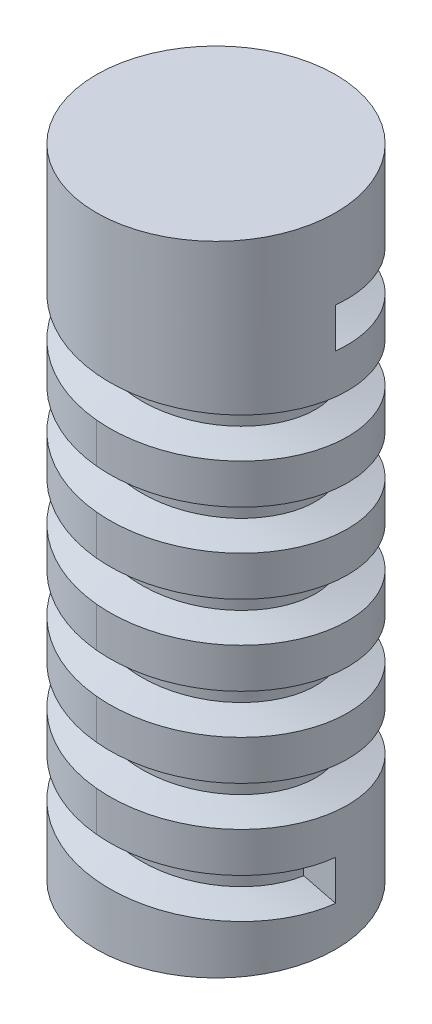
SolidWorks part; units mm, degrees
ref_plane "Front" through (0, 0, 0) normal (0, 0, 1) x (1, 0, 0)
ref_plane "Top" through (0, 0, 0) normal (0, 1, 0) x (1, 0, 0)
ref_plane "Right" through (0, 0, 0) normal (1, 0, 0) x (0, 0, -1)
sketch "Sketch1" plane through (0, 0, 0) normal (0, 1, 0) x (1, 0, 0)
  circle A0 centre (0, 0) radius 19.05
  dimension "D1" = 38.1
extrude "Boss-Extrude1" add sketch "Sketch1" along normal blind 101.6
sketch "Sketch2" plane through (0, 0, 0) normal (0, 0, 1) x (1, 0, 0)
  line L0 (13.97, 11.43) -> (13.97, 7.62)
  line L1 (13.97, 11.43) -> (19.05, 12.7)
  line L2 (13.97, 7.62) -> (19.05, 6.35)
  line L3 (-19.05, 0) -> (19.05, 0) construction
  line L4 (19.05, 12.7) -> (19.05, 6.35)
  dimension "D1" = 6.35
  dimension "D2" = 3.81
  dimension "D3" = 5.08
  dimension "D4" = 19.05
  dimension "D5" = 6.35
ref_plane "Plane1" through (0, 6.35, 0) normal (0, 1, 0) x (1, 0, 0)
sketch "Sketch3" plane through (0, 6.35, 0) normal (0, 1, 0) x (1, 0, 0)
  circle A0 centre (0, 0) radius 19.05
  dimension "D1" = 38.1
curve "Helix/Spiral1" pitch 12.7 height 76.2 radius 19.05 left hand yes centre (0, 6.35, 0) axis (0, 1, 0) start towards (1, 0, 0)
sweep "Cut-Sweep1" cut profiles "Sketch2" path "Helix/Spiral1"
